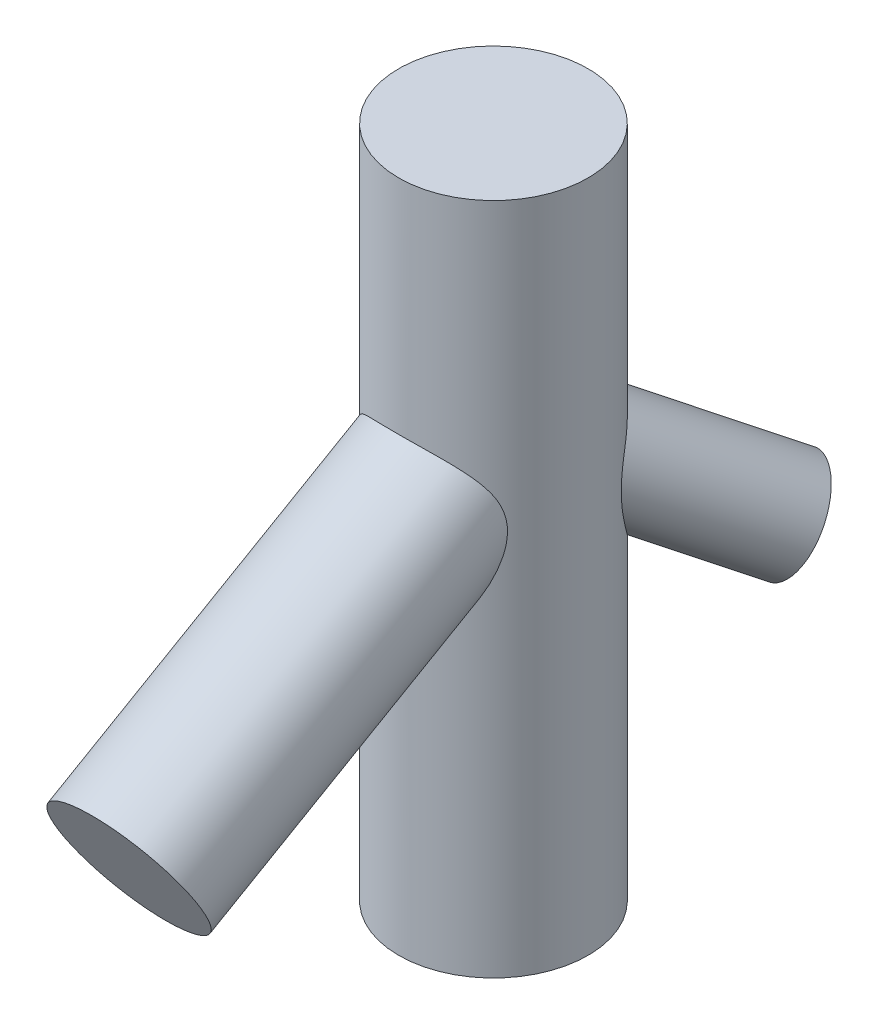
SolidWorks part; units mm, degrees
ref_plane "Front Plane" through (0, 0, 0) normal (0, 0, 1) x (1, 0, 0)
ref_plane "Top Plane" through (0, 0, 0) normal (0, 1, 0) x (1, 0, 0)
ref_plane "Right Plane" through (0, 0, 0) normal (1, 0, 0) x (0, 0, -1)
sketch "Sketch2" plane through (0, 0, 0) normal (0, 1, 0) x (1, 0, 0)
  circle A0 centre (0, 0) radius 11.25
  dimension "D1" = 22.5
extrude "Boss-Extrude1" add sketch "Sketch2" against normal blind 50 and the other way blind 30
sketch "Sketch3" plane through (0, 0, 0) normal (1, 0, 0) x (0, 0, -1)
  line L0 (0, 0) -> (-43.3013, -25) construction
  line L1 (12.375, 0) -> (-12.375, 0) construction
  point P5 (0, 0)
  dimension "D1" = 30
  dimension "D2" = 50
ref_plane "Plane1" through (0, -25, 43.3013) normal (0, -0.5, 0.866) x (1, 0, 0)
sketch "Sketch4" plane through (0, -25, 43.3013) normal (0, -0.5, 0.866) x (1, 0, 0)
  circle A0 centre (0, 0) radius 8.75
  dimension "D1" = 17.5
extrude "Boss-Extrude2" add sketch "Sketch4" against normal up to surface (31.9578 mm away) up to face at (0, 30, 11.25)
sketch "Sketch5" plane through (0, 0, 0) normal (0, 1, 0) x (1, 0, 0)
  line L0 (0, 0) -> (15.5366, 26.9102) construction
  line L1 (0, -41.0226) -> (0, 41.0226) construction
  point P5 (15.5366, 26.9102)
  dimension "D1" = 30
ref_axis "Axis2" through (0, 30, 0) along (0, -1, 0)
ref_plane "Plane5" through (0, 0, 0) normal (-0.866, 0, -0.5) x (-0.5, 0, 0.866)
ref_axis "Axis3" through (16.8759, 0, 0) along (-1, 0, 0)
ref_plane "Plane6" through (0, 0, 0) normal (0.866, 0, 0.5) x (0, -1, 0)
sketch "Sketch10" plane through (0, 0, 0) normal (0.866, 0, 0.5) x (0, -1, 0)
  line L0 (0, 0) -> (15, 25.9808) construction
  line L1 (0, 8.438) -> (0, -6.2947) construction
  dimension "D1" = 30
  dimension "D2" = 150
ref_plane "Plane7" through (12.9904, -15, -22.5) normal (0.433, -0.5, -0.75) x (-0.9014, -0.2402, -0.3603)
sketch "Sketch11" plane through (12.9904, -15, -22.5) normal (0.433, -0.5, -0.75) x (-0.9014, -0.2402, -0.3603)
  circle A0 centre (0, 0) radius 6
  dimension "D1" = 12
extrude "Boss-Extrude3" add sketch "Sketch11" against normal up to surface (20.4807 mm away) up to face at (0.2589, 3.6057, 11.247)
